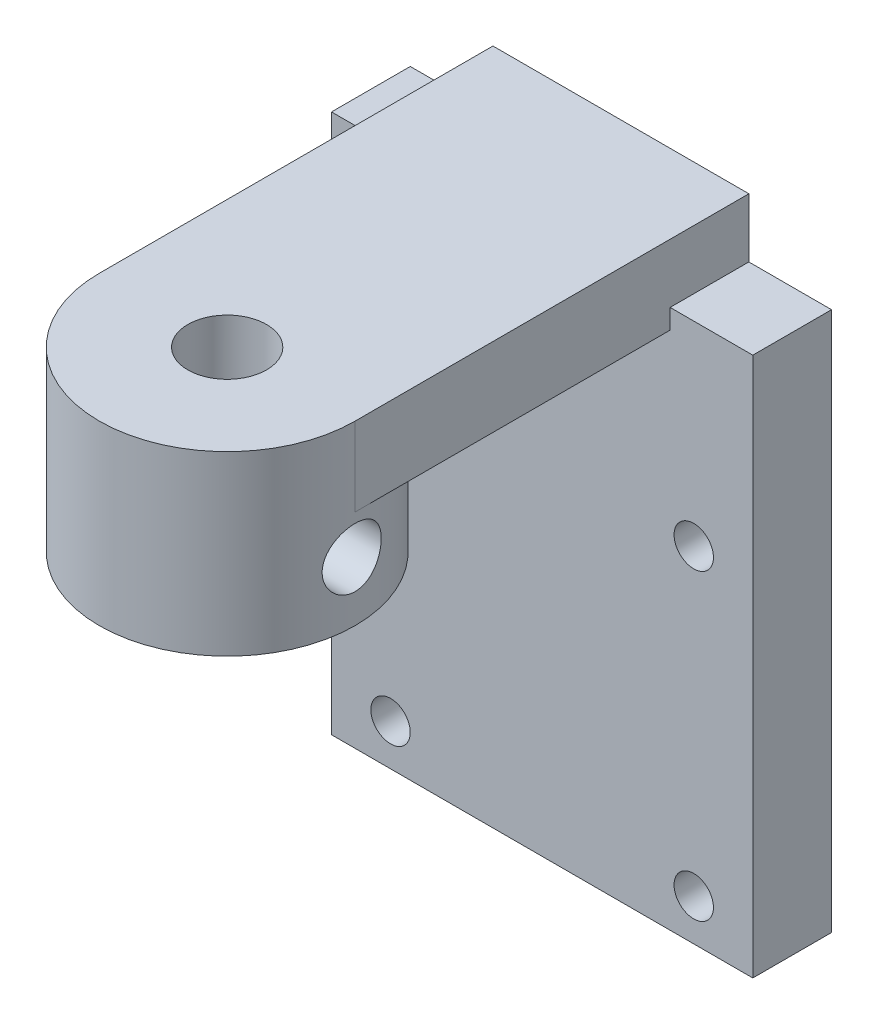
SolidWorks part; units mm, degrees
material "3.0205 (EN-AW 1200)"
ref_plane "前视基准面" through (0, 0, 0) normal (0, 0, 1) x (1, 0, 0)
ref_plane "上视基准面" through (0, 0, 0) normal (0, 1, 0) x (1, 0, 0)
ref_plane "右视基准面" through (0, 0, 0) normal (1, 0, 0) x (0, 0, -1)
sketch "草图1" plane through (0, 0, 0) normal (0, 1, 0) x (1, 0, 0)
  line L1 (5, 0) -> (2.5, 4.3301)
  line L2 (2.5, 4.3301) -> (-2.5, 4.3301)
  line L3 (-2.5, 4.3301) -> (-5, 0)
  line L4 (-5, 0) -> (-2.5, -4.3301)
  line L5 (-2.5, -4.3301) -> (2.5, -4.3301)
  line L6 (5, 0) -> (2.5, -4.3301)
sketch "草图2" plane through (0, 0, 0) normal (0, 1, 0) x (1, 0, 0)
  circle A0 centre (0, 0) radius 6.5
extrude "凸台-拉伸1" add sketch "草图2" along normal blind 9
sketch "草图3" plane through (0, 9, 0) normal (0, 1, 0) x (1, 0, 0)
  circle A0 centre (0, 0) radius 2
extrude "切除-拉伸2" cut sketch "草图3" against normal through all
sketch "草图4" plane through (0, 9, 0) normal (0, 1, 0) x (1, 0, 0)
  line L1 (6.5, 20) -> (4, 20)
  line L3 (-6.5, 0) -> (-6.5, 20)
  line L4 (-6.5, 20) -> (-4, 20)
  line L7 (-6.5, 0) -> (6.5, 0)
  line L8 (6.5, 0) -> (6.5, 20)
  line L11 (-4, 20) -> (4, 20)
  circle A0 centre (0, 0) radius 6.5 construction
  circle A1 centre (0, 0) radius 6.5
  circle M6 centre (0, 0) radius 6.5
extrude "凸台-拉伸2" add sketch "草图4" against normal blind 4 contours L4 L3 M6 | L8 L1 M6 region at (0, 9, -12.4819)
sketch "草图6" plane through (0, 0, -20) normal (0, 0, -1) x (-1, 0, 0)
  line L0 (10.7, 6) -> (-10.7, 6)
  line L1 (10.7, 6) -> (10.7, -21.4)
  line L2 (-10.7, 6) -> (10.7, 6)
  line L7 (10.7, 6) -> (10.7, -14.2408)
  line L8 (10.7, -21.4) -> (-10.7, -21.4)
  line L9 (-10.7, -21.4) -> (-10.7, 6)
  line M8 (-6.5, 5) -> (6.5, 5)
  line M9 (6.5, 5) -> (6.5, 9)
extrude "凸台-拉伸6" add sketch "草图6" against normal blind 4 contours L9 L8 L1 L0 M9 M8 region at (0, -7.7, -20)
sketch "草图17" plane through (0, 0, -16) normal (0, 0, 1) x (1, 0, 0)
  circle A0 centre (-7.7, -19.3) radius 1
  circle A1 centre (7.7, -19.3) radius 1
  circle A2 centre (7.7, -3.9) radius 1
  circle A3 centre (-7.7, -3.9) radius 1
extrude "切除-拉伸11" cut sketch "草图17" against normal blind 4
sketch "草图18" plane through (0, 0, 0) normal (0, -1, 0) x (1, 0, 0)
  circle A0 centre (0, 0) radius 2.5328
sketch "草图20" plane through (0, 0, 0) normal (1, 0, 0) x (0, 0, -1)
  line L0 (0, 9) -> (0, 3)
  circle A0 centre (0, 3) radius 1.5
extrude "切除-拉伸12" cut sketch "草图20" against normal through all both and the other way through all contours A0
